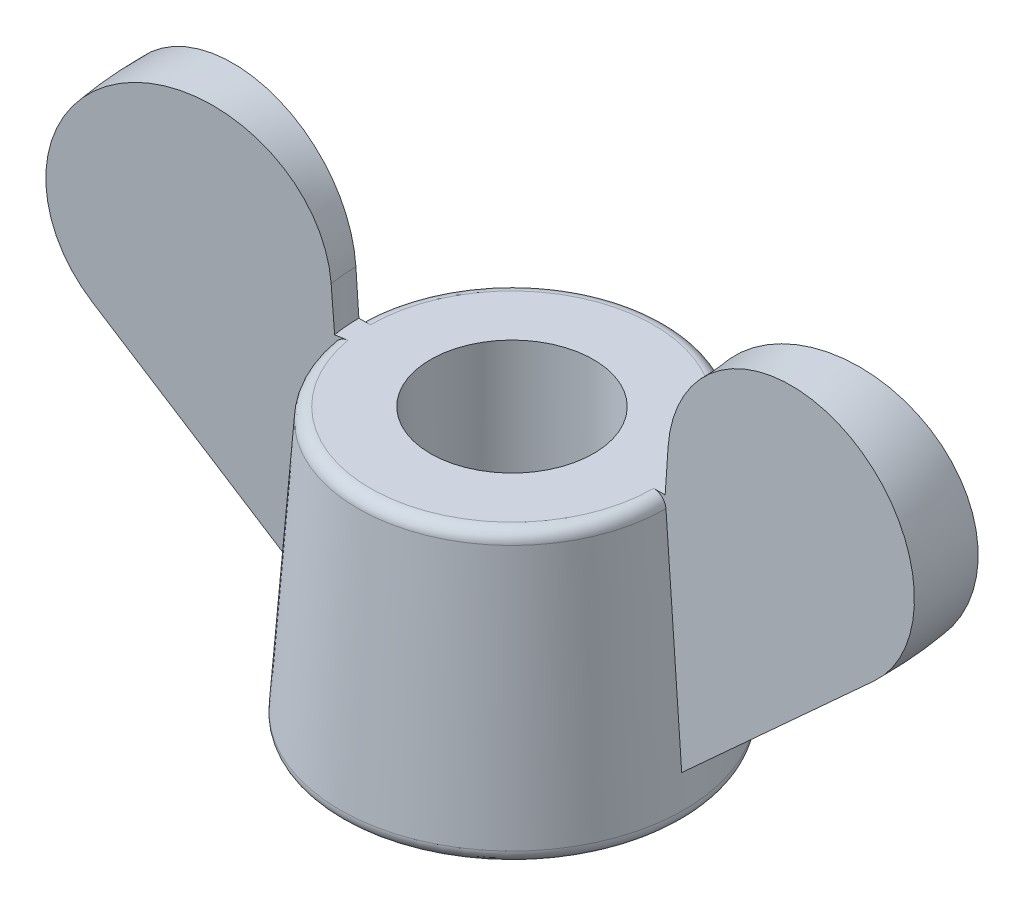
SolidWorks part; units mm, degrees
material "2014-O"
ref_plane "Plano frontal" through (0, 0, 0) normal (0, 0, 1) x (1, 0, 0)
ref_plane "Plano superior" through (0, 0, 0) normal (0, 1, 0) x (1, 0, 0)
ref_plane "Plano direito" through (0, 0, 0) normal (1, 0, 0) x (0, 0, -1)
sketch "Esboço1" plane through (0, 0, 0) normal (0, 0, 1) x (1, 0, 0)
  line L0 (0, 0) -> (3.5, 0)
  line L1 (0, 0) -> (0, 5.6)
  line L2 (0, 5.6) -> (3.1, 5.6)
  line L3 (3.1, 5.6) -> (3.5, 0)
  line L4 (0, 0) -> (0, 5.6)
  line L5 (5.6391, 8.8713) -> (5.8599, 8.8713)
  line L6 (8.1995, 6.5317) -> (8.1995, 6.3109)
  line L7 (3.1, 5.6) -> (3.3391, 6.8738)
  line L8 (3.5, 0) -> (7.6162, 4.8307)
  line L9 (3.1, 5.6) -> (3.5, 0)
  line L10 (3.5, 0) -> (0, 0)
  line L11 (0, 5.6) -> (0, 0)
  arc A0 (7.6162, 4.8307) -> (3.3391, 6.8738) centre (5.7495, 6.4213) ccw
  dimension "D1" = 2.45
  dimension "D2" = 2.45
revolve "Revolução2" add sketch "Esboço1" angle 360 about L1
sketch "Esboço3" plane through (0, 0, 0) normal (0, 0, 1) x (1, 0, 0)
  line L0 (0, 0) -> (3.4918, 0)
  line L1 (0, 0) -> (0, 5.6)
  line L3 (3.1, 5.6) -> (3.1597, 6.4707)
  line L4 (3.1, 5.6) -> (-3.1, 5.6) construction
  line L5 (3.4292, 0.896) -> (3.1, 5.6)
  line L7 (3.4292, 0.896) -> (7.3321, 4.4557)
  arc A0 (7.3321, 4.4557) -> (3.1597, 6.4707) centre (5.65, 6.3) ccw
revolve "Revolução3" add sketch "Esboço3" angle 10 about L1
sketch "Esboço4" plane through (0, 5.6, 0) normal (0, 1, 0) x (1, 0, 0)
  line L0 (0, 0) -> (0.343, -3.9202)
  line L4 (0.343, -3.9202) -> (-0.343, 3.9202)
  arc A1 (0.343, -3.9202) -> (-0.343, 3.9202) centre (0, 0) cw
  arc M3 (3.0529, 0.5383) -> (3.1, 0) centre (0, 0) ccw
extrude "Corte-extrusão2" cut sketch "Esboço4" against normal blind 10 contours L0 L4 M3 | A1 L0 L4 M3
mirror "Espelhar1" of bodies 104
hole_wizard "Broca de rosquear para tarraxa de M41" positions "Esboço6" profile "Esboço5" hole size "M4" standard "ISO"
sketch "Esboço6" plane through (0, 5.6, 0) normal (0, 1, 0) x (1, 0, 0)
  point P0 (0, 0)
sketch "Esboço5" plane through (0, 5.6, 0) normal (1, 0, 0) x (0, 0, 1)
  line L0 (0, 0) -> (0, 10.9914)
  line L1 (0, 10.9914) -> (1.65, 10)
  line L2 (1.65, 10) -> (1.65, 0)
  line L5 (1.65, 0) -> (0, 0)
  line L10 (0, 10.9914) -> (-1.65, 10) construction
  line L11 (0, -6.35) -> (0, 107.95) construction
  dimension "Hole Dia." = 3.3
  dimension "Hole Depth" = 10
  dimension "Drill Angle" = 118
fillet "Filete1" radius 0.25 3 edges at (-0.2702, 5.6, -3.0882) (0.2702, 5.6, 3.0882) (0, 0, -3.5)
